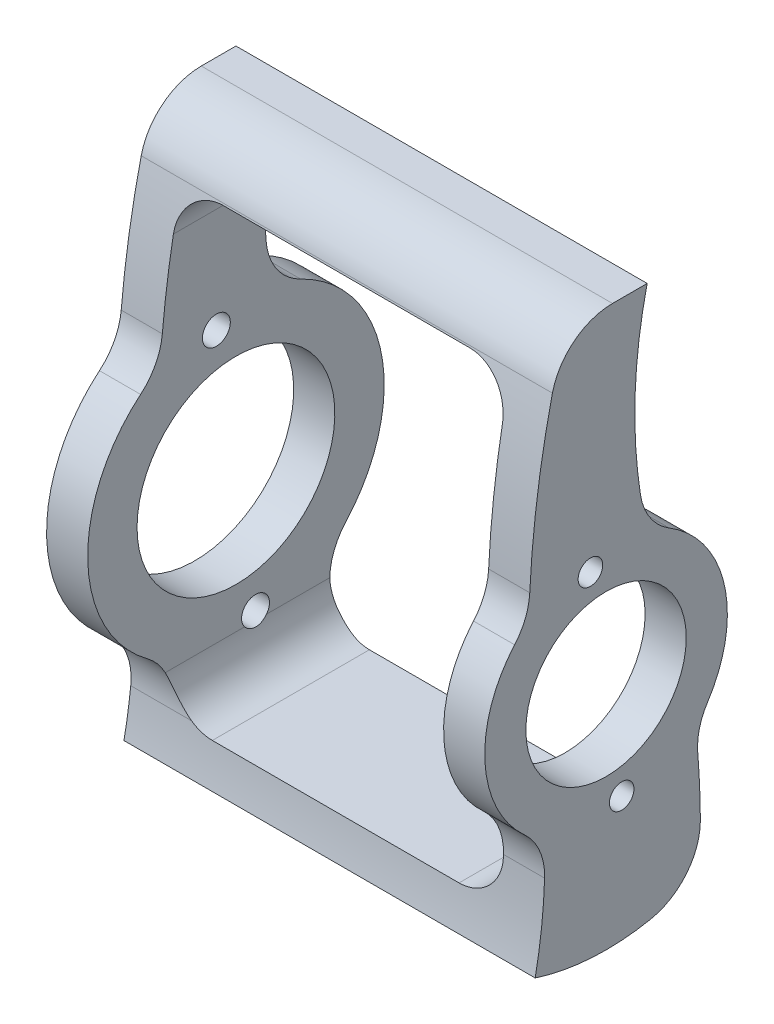
SolidWorks part; units mm, degrees
other "Markup2"
sketch "Sketch9" plane through (31.75, 50.4016, 20.35) normal (0.8402, 0.4575, 0.2911) x (0.3274, 0, -0.9449)
material "AISI 4340 Steel, normalized"
ref_plane "Front Plane" through (0, 0, 0) normal (0, 0, 1) x (1, 0, 0)
ref_plane "Top Plane" through (0, 0, 0) normal (0, 1, 0) x (1, 0, 0)
ref_plane "Right Plane" through (0, 0, 0) normal (1, 0, 0) x (0, 0, -1)
other "Center of Mass"
sketch "Weapon Layout" plane through (0, 0, 0) normal (1, 0, 0) x (0, 0, -1)
  line L0 (-6.35, 50.4016) -> (6.35, 50.4016) construction
  line L1 (-10.9443, -33.834) -> (14.4209, -32.5046) construction
  line L2 (6.35, 50.4016) -> (-5.4537, 0) construction
  line L3 (6.35, 50.4016) -> (0, 0) construction
  line L4 (0, 0) -> (0, -33.2604) construction
  circle A0 centre (0, 0) radius 14 construction
  circle A1 centre (0, 0) radius 50.8 construction
  circle A2 centre (0, 0) radius 17.175 construction
  circle A3 centre (0, 0) radius 20.35 construction
  arc A4 (-6.35, 50.4016) -> (-20.35, 0) centre (77.3756, 0) ccw construction
  arc A5 (23.3803, -26.7932) -> (-23.7089, -26.5029) centre (0, 0) cw construction
  arc A6 (6.35, 50.4016) -> (15.4347, 13.2625) centre (47.4536, 40.7754) ccw construction
  dimension "D1" = 28
  dimension "D2" = 101.6
  dimension "D3" = 3.175
  dimension "D4" = 6.35
  dimension "D5" = 12.7
  dimension "D7" = 6
  dimension "D6" = 15.24
  dimension "D8" = 25.4
  dimension "D9" = 87
sketch "Sketch2" plane through (0, 0, 0) normal (1, 0, 0) x (0, 0, -1)
  line L0 (-6.35, 50.4016) -> (6.35, 50.4016)
  line L1 (-11.3249, -1.5462) -> (0, 0) construction
  line L2 (6.35, 50.4016) -> (-5.4537, 0) construction
  line L3 (-11.5714, 0.7977) -> (-15.24, 50.4016) construction
  arc A0 (-10.9443, -33.834) -> (14.4209, -32.5046) centre (0, 0) ccw
  arc A1 (-23.7089, -26.5029) -> (23.3803, -26.7932) centre (0, 0) ccw construction
  arc A2 (-10.934, -3.8704) -> (-11.5714, 0.7977) centre (26.4248, 3.6078) cw
  arc A3 (9.7952, 6.5275) -> (11.7704, 0.1087) centre (-25.4904, -7.8439) cw
  arc A4 (-11.5714, 0.7977) -> (-6.35, 50.4016) centre (128.3504, 11.1461) cw
  arc A5 (-10.934, -3.8704) -> (-10.9443, -33.834) centre (-85.6518, -18.8267) cw
  arc A6 (6.35, 50.4016) -> (9.7952, 6.5275) centre (76.9323, 33.8717) ccw
  arc A7 (11.7704, 0.1087) -> (14.4209, -32.5046) centre (-112.4323, -26.3999) cw
  circle A9 centre (0, 0) radius 11.43 construction
  point P25 (10.9245, 3.3617)
  dimension "D1" = 127
  dimension "D2" = 38.1
  dimension "D3" = 76.2
  dimension "D4" = 38.1
  dimension "D5" = 22.86
  dimension "D6" = 8.89
extrude "Boss-Extrude2" add sketch "Sketch2" along normal mid plane 63.5
sketch "Sketch3" plane through (0, 0, 0) normal (0, 0, 1) x (1, 0, 0)
  line L0 (31.75, 50.4016) -> (-31.75, 50.4016) construction
  line L1 (-25.4, 42.7816) -> (25.4, 42.7816)
  line L2 (-25.4, 42.7816) -> (-25.4, -27.94)
  line L3 (-25.4, -27.94) -> (25.4, -27.94)
  line L4 (25.4, 42.7816) -> (25.4, -27.94)
  line L6 (-31.75, -35.56) -> (31.75, -35.56) construction
  line L7 (-31.75, 50.4016) -> (-31.75, 0.7977) construction
  dimension "D1" = 7.62
  dimension "D3" = 6.35
  dimension "D4" = 7.62
  dimension "D2" = 6.35
extrude "Cut-Extrude1" cut sketch "Sketch3" against normal through all both and the other way through all
fillet "Fillet1" radius 6.35 4 edges at (-25.4, 42.7816, 1.6753) (25.4, 42.7816, 1.6753) (25.4, -27.94, -2.2798) (-25.4, -27.94, -2.2798)
fillet "Fillet3" radius 9.525 2 edges at (0, -32.5046, -14.4209) (0, 50.4016, 6.35)
sketch "Sketch6" plane through (-31.75, 0, 0) normal (-1, 0, 0) x (0, 0, 1)
  circle A0 centre (0, 0) radius 22.89
  point P2 (0, 0)
  dimension "D1" = 45.78
extrude "Boss-Extrude3" add sketch "Sketch6" against normal up to surface (6.35 mm away) up to face at (-25.4, 4.1451, 0.3502)
sketch "Sketch7" plane through (-31.75, 0, 0) normal (-1, 0, 0) x (0, 0, 1)
  circle A0 centre (0, 0) radius 15.27
  arc A1 (9.4783, -20.8354) -> (11.6939, 19.6775) centre (0, 0) ccw construction
  dimension "D1" = 30.54
extrude "Cut-Extrude3" cut sketch "Sketch7" against normal up to next
sketch "Sketch10" plane through (31.75, 0, 0) normal (1, 0, 0) x (0, 0, -1)
  circle A0 centre (0, 0) radius 18.7325
  dimension "D1" = 37.465
extrude "Boss-Extrude4" add sketch "Sketch10" against normal up to surface (6.35 mm away) up to face at (25.4, 4.1451, 0.3502)
sketch "Sketch5" plane through (31.75, 0, 0) normal (1, 0, 0) x (0, 0, -1)
  circle A0 centre (0, 0) radius 12.3825
  circle A1 centre (0, 0) radius 6.35 construction
  dimension "D1" = 12.7
  dimension "D2" = 24.765
extrude "Cut-Extrude2" cut sketch "Sketch5" against normal up to next
fillet "Fillet2" radius 9.525 8 edges at (-28.575, 19.6775, 11.6939) (-28.575, -20.8354, 9.4783) (-28.575, -17.8878, -14.2821) (-28.575, 22.2493, -5.378) (28.575, 17.6489, -6.2788) (28.575, -12.645, -13.8207) (28.575, -16.1454, 9.499) (28.575, 14.4551, 11.9145)
sketch "Sketch11" plane through (31.75, 0, 0) normal (1, 0, 0) x (0, 0, -1)
  circle A0 centre (-2.4136, 16.1721) radius 1.8986
  circle A1 centre (-2.4136, 16.1721) radius 1.8986 construction
  circle A2 centre (2.4136, -16.1721) radius 1.8987
  circle A3 centre (2.4136, -16.1721) radius 1.8986 construction
extrude "Cut-Extrude4" cut sketch "Sketch11" against normal up to surface (6.35 mm away) up to face at (25.4, 12.3825, 0)
hole_wizard "#6 Clearance Hole1" positions "Sketch12" profile "Sketch13" hole size "#6" standard "ANSI Inch"
sketch "Sketch12" plane through (-31.75, 0, 0) normal (1, 0, 0) x (0, 0, -1)
  point P0 (-3.0235, 20.259)
  point P3 (3.0235, -20.259)
sketch "Sketch13" plane through (-31.75, 20.259, 3.0235) normal (0, 1, 0) x (0, 0, 1)
  line L0 (0, 0) -> (0, 8.9134)
  line L1 (0, 8.9134) -> (2.1526, 7.62)
  line L2 (2.1526, 7.62) -> (2.1526, 0)
  line L5 (2.1526, 0) -> (0, 0)
  line L10 (0, 8.9134) -> (-2.1527, 7.62) construction
  line L11 (0, -6.35) -> (0, 107.95) construction
  dimension "Hole Dia." = 4.3053
  dimension "Hole Depth" = 7.62
  dimension "Drill Angle" = 118
equation "\"D1@Weapon Layout\" = 28mm"
equation "\"D1@Sketch6\"=\"bearing OD L\"+1/2in+0.2in"
equation "\"D2@Sketch3\"=\"D3@Sketch3\""
equation "\"D1@Sketch7\"=\"bearing OD L\"+0.1in"
equation "\"D2@Sketch5\"=\"bearing OD R\" + .1"
equation "\"D1@Sketch10\"=\"bearing OD R\" + 1/2 + .1"
equation "\"bearing OD R\" = 7 / 8"
equation "\"bearing OD L\"= 28mm"
